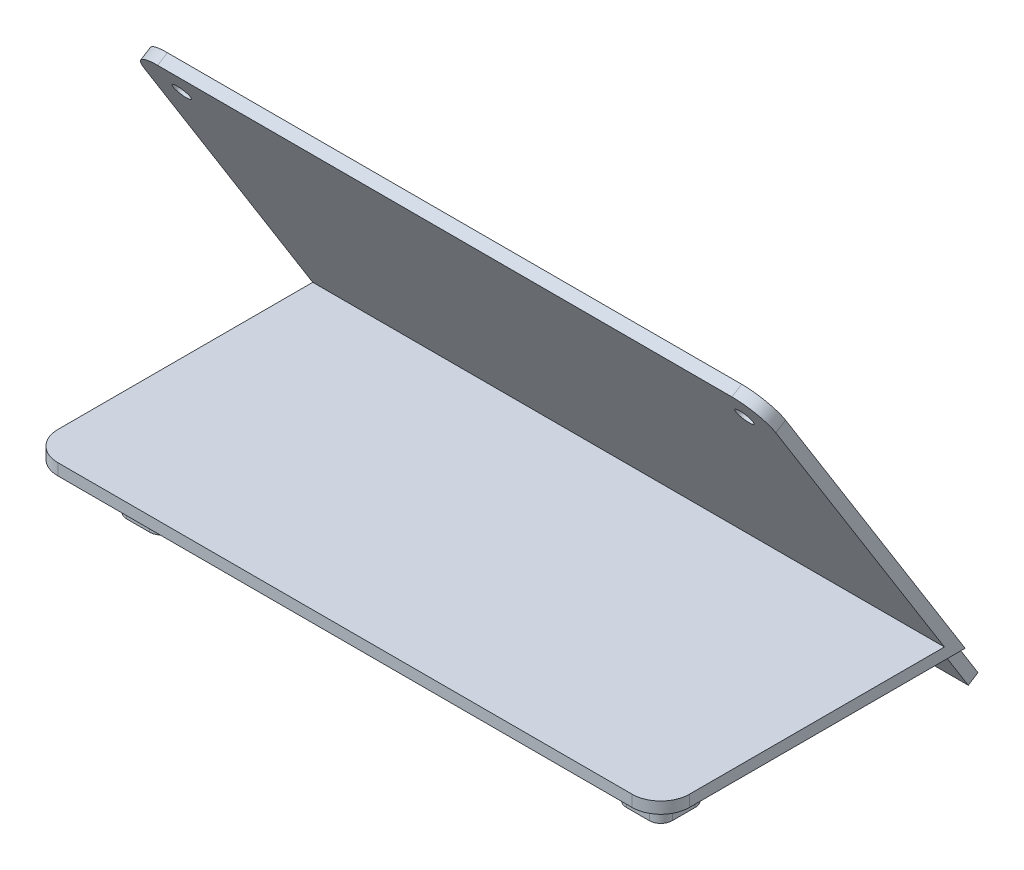
SolidWorks part; units mm, degrees
ref_plane "Front Plane" through (0, 0, 0) normal (0, 0, 1) x (1, 0, 0)
ref_plane "Top Plane" through (0, 0, 0) normal (0, 1, 0) x (1, 0, 0)
ref_plane "Right Plane" through (0, 0, 0) normal (1, 0, 0) x (0, 0, -1)
sketch "Sketch1" plane through (0, 0, 0) normal (0, 1, 0) x (1, 0, 0)
  line L1 (-55, -26.5) -> (55, -26.5)
  line L2 (-55, -26.5) -> (-55, 26.5)
  line L3 (-55, 26.5) -> (55, 26.5)
  line L4 (55, -26.5) -> (55, 26.5)
  line L5 (-55, -26.5) -> (55, 26.5) construction
  line L6 (-55, 26.5) -> (55, -26.5) construction
  point P0 (0, 0)
  dimension "D1" = 110
  dimension "D2" = 53
extrude "Boss-Extrude1" add sketch "Sketch1" along normal blind 2
ref_plane "Plane1" through (0, 11.909, -19.0584) normal (0, 0.5299, -0.848) x (-1, 0, 0)
sketch "Sketch2" plane through (0, 11.909, -19.0584) normal (0, 0.5299, -0.848) x (-1, 0, 0)
  line L0 (-55, -12.3468) -> (55, -12.3468) construction
  line L2 (-55, -12.3468) -> (-55, 49.9632)
  line L3 (-55, 49.9632) -> (55, 49.9632)
  line L4 (55, -12.3468) -> (55, 49.9632)
  line L6 (-53, -12.3468) -> (-53, -22.0468)
  line L7 (-53, -22.0468) -> (-45, -22.0468)
  line L9 (-55, -12.3468) -> (-53, -12.3468)
  line L10 (0, 1.1) -> (0, -1.1) construction
  line L11 (55, -12.3468) -> (53, -12.3468)
  line L13 (53, -22.0468) -> (45, -22.0468)
  line L14 (53, -12.3468) -> (53, -22.0468)
  line L17 (45, -22.0468) -> (-45, -22.0468)
  circle A0 centre (-49, 43.9632) radius 1.5
  circle A1 centre (-49, -16.0368) radius 1.5
  circle A2 centre (49, 43.9632) radius 1.5
  circle A3 centre (49, -16.0368) radius 1.5
  dimension "D4" = 3
  dimension "D9" = 3
  dimension "D2" = 62.31
  dimension "D3" = 6
  dimension "D5" = 6
  dimension "D6" = 2
  dimension "D7" = 9.7
  dimension "D8" = 60
  dimension "D10" = 4
extrude "Boss-Extrude2" add sketch "Sketch2" against normal blind 2
sketch "Sketch3" plane through (0, 11.909, -19.0584) normal (0, 0.5299, -0.848) x (-1, 0, 0)
  line L1 (-55, -11.6845) -> (55, -11.6845)
  line L2 (-55, -11.6845) -> (-55, -14.1845)
  line L3 (-55, -14.1845) -> (55, -14.1845)
  line L4 (55, -11.6845) -> (55, -14.1845)
  dimension "D1" = 110
  dimension "D2" = 2.5
extrude "Cut-Extrude1" cut sketch "Sketch3" along normal blind 2
sketch "Sketch8" plane through (0, 0, 0) normal (0, -1, 0) x (1, 0, 0)
  line L0 (-55, -26.5) -> (-55, 26.5) construction
  line L1 (-47.5, 19) -> (-39.5, 19)
  line L2 (-47.5, 19) -> (-47.5, 11)
  line L3 (-47.5, 11) -> (-39.5, 11)
  line L4 (-39.5, 19) -> (-39.5, 11)
  line L5 (-55, 26.5) -> (55, 26.5) construction
  line L6 (0, -1.1) -> (0, 1.1) construction
  line L7 (39.5, 19) -> (39.5, 11)
  line L8 (47.5, 11) -> (39.5, 11)
  line L9 (47.5, 19) -> (47.5, 11)
  line L10 (47.5, 19) -> (39.5, 19)
  circle A0 centre (-43.5, 15) radius 1.5
  circle A1 centre (43.5, 15) radius 1.5
  point P10 (0, 0)
  dimension "D5" = 3
  dimension "D1" = 7.5
  dimension "D2" = 8
  dimension "D3" = 7.5
  dimension "D4" = 8
  dimension "D6" = 4
  dimension "D7" = 4
extrude "Boss-Extrude5" add sketch "Sketch8" along normal blind 8
fillet "Fillet1" radius 5 4 edges at (55, 1, 26.5) (-55, 1, 26.5) (55, 53.7503, 8.2661) (-55, 53.7503, 8.2661)
fillet "Fillet2" radius 2 16 edges at (-43.5, 0, 19) (-43.5, 0, 11) (-39.5, -4, 11) (-39.5, -4, 19) (-39.5, 0, 15) (-47.5, -4, 19) (-47.5, -4, 11) (-47.5, 0, 15) (47.5, 0, 15) (43.5, 0, 19) (43.5, 0, 11) (47.5, -4, 19) (39.5, -4, 19) (47.5, -4, 11) (39.5, 0, 15) (39.5, -4, 11)
